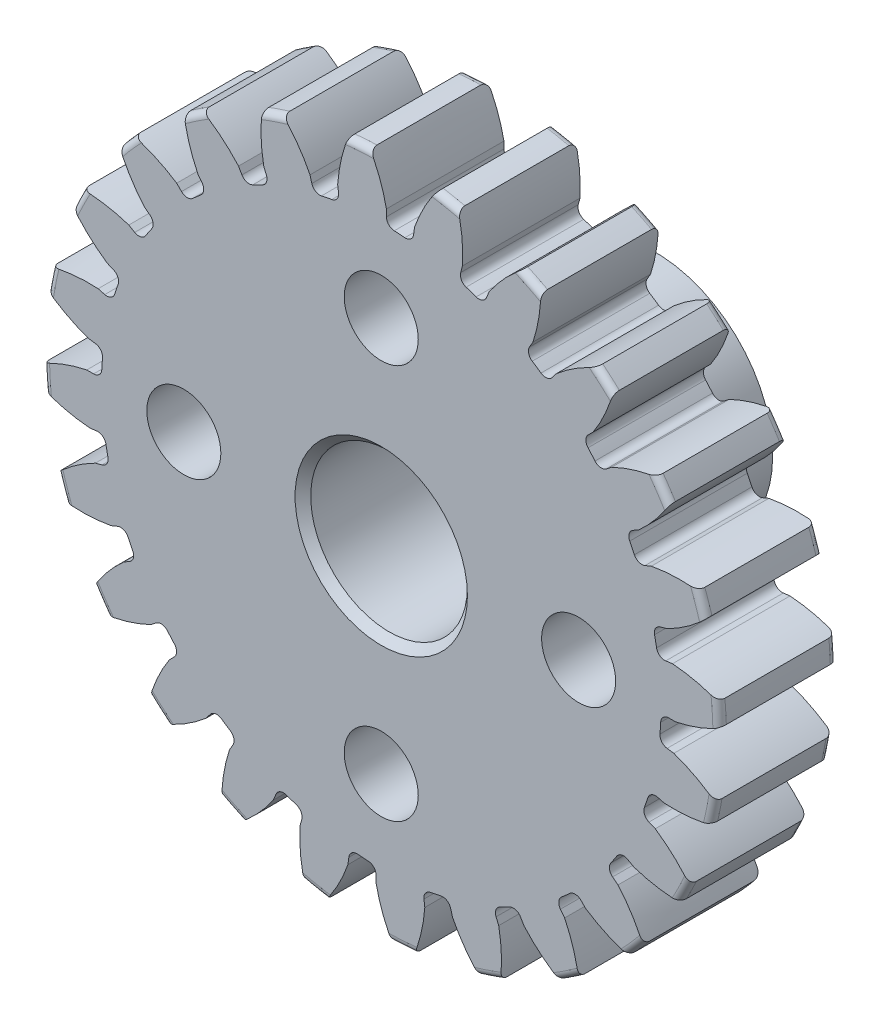
SolidWorks part; units mm, degrees
ref_plane "Front" through (0, 0, 0) normal (0, 0, 1) x (1, 0, 0)
ref_plane "Top" through (0, 0, 0) normal (0, 1, 0) x (1, 0, 0)
ref_plane "Right" through (0, 0, 0) normal (1, 0, 0) x (0, 0, -1)
sketch "Sketch1" plane through (0, 0, 0) normal (0, 0, 1) x (1, 0, 0)
  line L0 (-304.8, 0) -> (304.8, 0) construction
  circle A0 centre (0, 0) radius 13.716
  circle A1 centre (0, 0) radius 12.7 construction
  circle A3 centre (0, 0) radius 11.3348 construction
  dimension "D1" = 2.3812
extrude "Boss-Extrude1" add sketch "Sketch1" against normal blind 4.7625
sketch "Sketch2" plane through (0, 0, 0) normal (1, 0, 0) x (0, 0, -1)
  line L0 (4.7625, 0) -> (11.0998, 0)
  line L1 (4.7625, 0) -> (4.7625, 6.35)
  line L2 (4.7625, 6.35) -> (11.0998, 6.35)
  line L3 (11.0998, 6.35) -> (11.0998, 0)
  point P5 (11.0998, -6.35)
  point P6 (0, -13.716)
  point P7 (4.7625, -13.716)
  point P9 (0, 13.716)
revolve "Revolve1" add sketch "Sketch2" angle 360 mid plane about L0
fillet "Fillet2" radius 0.2743 3 edges at (13.716, 0, -4.7625) (13.716, 0, 0) (6.35, 0, -4.7625)
sketch "Sketch3" plane through (0, 0, 0) normal (0, 0, 1) x (1, 0, 0)
  line L0 (0, 0) -> (0, 13.716) construction
  line L1 (-4.0817, 11.2144) -> (0, 12.7)
  line L2 (-9.5921, 12.7) -> (9.5921, 12.7) construction
  line L3 (-9.0136, 9.4193) -> (9.0136, 15.9807) construction
  line L4 (-4.0817, 11.2144) -> (0, 0) construction
  line L5 (-9.8295, 6.7678) -> (0, 0) construction
  line L6 (-9.8295, 6.7678) -> (-3.193, 16.4066) construction
  line L7 (-2.8353, 11.5924) -> (0, 0) construction
  line L8 (-2.8353, 11.5924) -> (0.1182, 12.3148) construction
  arc A0 (-4.0817, 11.2144) -> (-9.8295, 6.7678) centre (0, 0) ccw
  circle A1 centre (0, 0) radius 12.7 construction
  circle A2 centre (0, 0) radius 11.9341 construction
  arc A3 (-4.0817, 11.2144) -> (-2.8353, 11.5924) centre (0, 0) cw
  circle A4 centre (0, 0) radius 13.716 construction
  point P6 (0, 12.7)
  dimension "D1" = 4.3437
  dimension "D3" = 11.7025
  dimension "D5" = 3.0406
  dimension "D2" = 7.3842
  dimension "D4" = 1.3031
sketch "Sketch4" plane through (0, 0, 0) normal (0, 0, 1) x (1, 0, 0)
  line L0 (0, 0) -> (0.8288, 12.6457) construction
  line L1 (0.2102, 11.9322) -> (0.2102, 11.3328)
  line L2 (0, 12.7) -> (1.6577, 12.5913) construction
  line L3 (1.3491, 11.8576) -> (1.2708, 11.2633)
  line L4 (0.2102, 11.3328) -> (0, 0) construction
  line L5 (0, 0) -> (0, 13.716) construction
  line L6 (-9.8295, 6.7678) -> (-3.193, 16.4066) construction
  line L7 (-9.8295, 6.7678) -> (-3.193, 16.4066) construction
  arc A0 (1.2708, 11.2633) -> (0.2102, 11.3328) centre (0, 0) ccw
  arc A1 (0, 12.7) -> (1.6577, 12.5913) centre (0, 0) cw construction
  circle A2 centre (0, 0) radius 12.7 construction
  circle A3 centre (0, 0) radius 11.9341 construction
  circle A4 centre (0, 0) radius 11.3348 construction
  arc A5 (5.3072, 15.8494) -> (-3.193, 16.4066) centre (0, 0) ccw
  spline S0 degree 2 poles (-3.193, 16.4066) (-0.3735, 14.7207) (0.2102, 11.9322) knots 0 0 0 1 1 1
  spline S1 degree 2 poles (5.3072, 15.8494) (2.2918, 14.5461) (1.3491, 11.8576) knots 0 0 0 1 1 1
  dimension "D1" = 1.6624
extrude "Cut-Extrude1" cut sketch "Sketch4" against normal through all
fillet "Fillet1" radius 0.3325 2 edges at (1.2708, 11.2633, -2.3813) (0.2102, 11.3328, -2.3813)
pattern_circular "CirPattern1" count 24 over 360 about axis through (0, 0, -4.7625) along (0, 0, 1) of "Cut-Extrude1", "Fillet1"
sketch "Sketch5" plane through (0, 0, 0) normal (0, 0, 1) x (1, 0, 0)
  line L0 (0, 4.3663) -> (0, 0) construction
  line L1 (-1.1906, 2.9433) -> (1.1906, 2.9433) construction
  line L2 (-1.1906, 2.9433) -> (-1.1906, 4.3663) construction
  line L3 (-1.1906, 4.3663) -> (1.1906, 4.3663) construction
  line L4 (1.1906, 2.9433) -> (1.1906, 4.3663) construction
  line L5 (-1.1906, 2.9433) -> (1.1906, 4.3663) construction
  line L6 (-1.1906, 4.3663) -> (1.1906, 2.9433) construction
  circle A0 centre (0, 0) radius 3.175
  point P3 (0, 3.6548)
  point P8 (0, 3.175)
  point P9 (0, -3.175)
  dimension "Bore Min" = 6.35
  dimension "Keyway Wd" = 2.3813
  dimension "Keyway Dpt." = 1.1913
extrude "Cut-Extrude2" cut sketch "Sketch5" against normal through all
chamfer "Chamfer1" distance 0.3175 angle 45 3 edges at (6.35, 0, -11.0998) (3.175, 0, 0) (3.175, 0, -11.0998)
sketch "Pitch Dia" plane through (0, 0, 0) normal (0, 0, 1) x (1, 0, 0)
  circle A0 centre (0, 0) radius 12.7 construction
  circle A1 centre (0, 0) radius 12.7 construction
sketch "Sketch19" plane through (0, 0, -4.7625) normal (0, 0, -1) x (-1, 0, 0)
  circle A0 centre (0, 0) radius 4.7625
  dimension "D1" = 9.525
extrude "Cut-Extrude9" cut sketch "Sketch19" along normal through all flip side to cut
sketch "Sketch20" plane through (0, 0, -4.7625) normal (0, 0, -1) x (-1, 0, 0)
  line L0 (0, 15.0033) -> (0, -15.1457) construction
  line L1 (-18.4026, 0) -> (14.9499, 0) construction
  circle A0 centre (0, 7.9997) radius 1.5
  circle A1 centre (7.9997, 0) radius 1.5
  circle A2 centre (0, -7.9997) radius 1.5
  circle A3 centre (-7.9997, 0) radius 1.5
  dimension "D1" = 3
  dimension "D2" = 3
  dimension "D3" = 3
  dimension "D4" = 3
  dimension "D5" = 15.9995
  dimension "D6" = 15.9995
extrude "Cut-Extrude8" cut sketch "Sketch20" against normal through all contours A3 | A0 | A1 | A2 region at (0, 7.9997, -4.7625) region at (-7.9997, 0, -4.7625) region at (0, -7.9997, -4.7625) region at (7.9997, 0, -4.7625)
chamfer "Chamfer4" distance 1.5 angle 45 4 edges at (-1.5, -7.9997, -4.7625) (-9.4997, 0, -4.7625) (-1.5, 7.9997, -4.7625) (6.4997, 0, -4.7625)
sketch "Sketch21" plane through (0, 0, 0) normal (0, 1, 0) x (1, 0, 0)
  line L0 (0, 10.7823) -> (0, 0.3175) construction
  line L2 (-0.3071, 4.7625) -> (-1.4495, 4.7625) construction
  circle A0 centre (0, 6.985) radius 0.9525
  point P4 (0, 0)
  point P6 (0, 6.0325)
  dimension "D1" = 1.905
  dimension "D2" = 1.27
extrude "Cut-Extrude10" cut sketch "Sketch21" against normal through all both and the other way through all
equation "\"D1@Boss-Extrude1\" = \"Face Wd@Sketch2\""
equation "\"D2@Sketch3\"= \"D1@Sketch3\" * 1.7"
equation "\"D3@Sketch3\"= \"D1@Sketch3\" + \"D2@Sketch3\" - .001"
equation "\"D4@Sketch3\" = \"D1@Sketch3\"*.3"
equation "\"D5@Sketch3\" = \"D1@Sketch3\"-\"D4@Sketch3\""
equation "\"D1@Sketch4\" = 1.5708/(\"Number of Teeth@Sketch1\"/\"Ptich Dia@Sketch1\")"
equation "\"D1@Chamfer1\" = \"B Hub Dia@Sketch2\"*.025"
equation "\"D1@CirPattern1\" = \"Number of Teeth@Sketch1\""
equation "\"D1@Fillet1\" = \"D1@Sketch4\"*.2"
equation "\"D1@Fillet2\" = \"OD@Sketch1\"*.01"
equation "\"D1@Sketch1\" = 2.250/(\"Number of Teeth@Sketch1\"/\"Ptich Dia@Sketch1\")"
